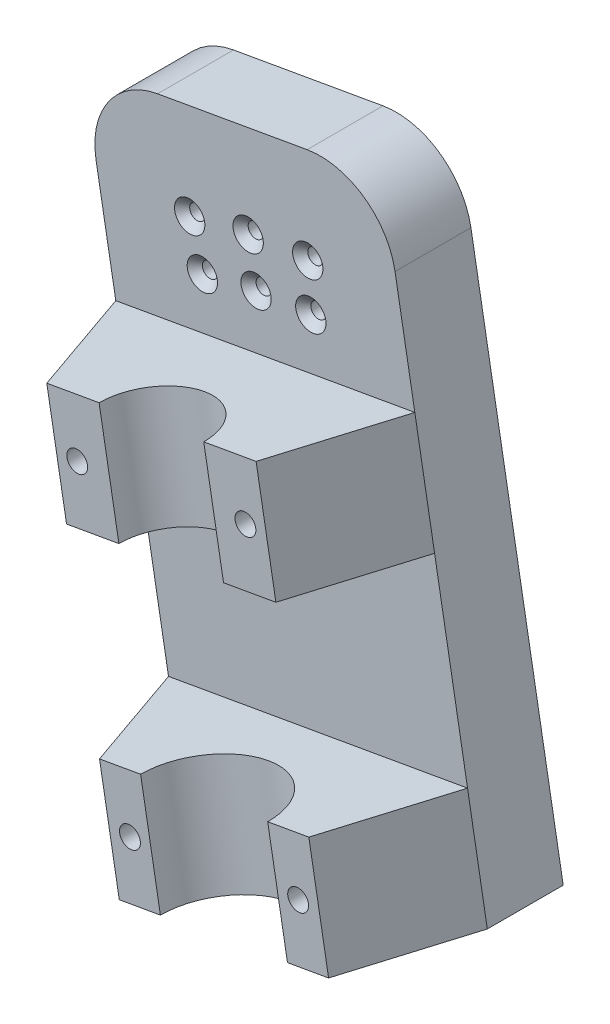
SolidWorks part; units mm, degrees
ref_plane "Front Plane" through (0, 0, 0) normal (0, 0, 1) x (1, 0, 0)
ref_plane "Top Plane" through (0, 0, 0) normal (0, 1, 0) x (1, 0, 0)
ref_plane "Right Plane" through (0, 0, 0) normal (1, 0, 0) x (0, 0, -1)
sketch "Sketch1" plane through (0, 0, 0) normal (0, 0, 1) x (1, 0, 0)
  line L0 (0, 62) -> (0, 74) construction
  line L1 (-20.5532, 71.0884) -> (-5, 73.8309) construction
  line L2 (0, 68) -> (0, 74)
  line L4 (0, 62) -> (0, 75.8947)
  line L5 (0, 0) -> (0, 79.9318) construction
  line L6 (0, 0) -> (-27.3383, 75.1113) construction
  line L7 (-27.3383, 75.1113) -> (-21.2052, 58.2609)
  line L8 (-20.5532, 71.0884) -> (0, 0) construction
  line L9 (0, 0) -> (-5, 73.8309) construction
  line L10 (-12.85, 72.8758) -> (-12.7766, 72.4597) construction
  line L13 (-12.7766, 72.4597) -> (-5.1015, 28.9321) construction
  line L16 (-5.1015, 28.9321) -> (-15.4722, 87.7473) construction
  line L17 (-34.6299, 81.2205) -> (4.7624, 88.1664)
  line L18 (-34.6299, 81.2205) -> (-20.738, 2.4359)
  line L19 (4.7624, 88.1664) -> (18.6543, 9.3818)
  line L20 (-20.738, 2.4359) -> (18.6543, 9.3818)
  arc A0 (0, 68) -> (-23.2574, 63.8991) centre (0, 0) ccw
  arc A1 (0, 74) -> (-25.3095, 69.5373) centre (0, 0) ccw
  arc A2 (-4.1389, 79.8245) -> (-27.3383, 75.1113) centre (0, 0) ccw
  arc A3 (0, 62) -> (-21.2052, 58.2609) centre (0, 0) ccw
  arc A5 (0, 75.8947) -> (-4.1389, 79.8245) centre (-3.9352, 75.8947) ccw
  circle A6 centre (-20.5532, 71.0884) radius 1
  circle A7 centre (-5, 73.8309) radius 1
  circle A8 centre (-18.8867, 65.3245) radius 1
  circle A9 centre (-4.5946, 67.8446) radius 1
  circle A10 centre (-12.85, 72.8758) radius 1
  circle A11 centre (-11.8081, 66.9669) radius 1
  point P31 (-80, 0)
  dimension "D1" = 79.9318
  dimension "D2" = 62
  dimension "D3" = 68
  dimension "D4" = 74
  dimension "D5" = 20
  dimension "D6" = 40
  dimension "D7" = 2
  dimension "D8" = 2
  dimension "D10" = 5
  dimension "D11" = 2
  dimension "D12" = 2
  dimension "D13" = 80
  dimension "D16" = 2
  dimension "D17" = 2
  dimension "D15" = 12
  dimension "D9" = 5
  dimension "D14" = 20
extrude "Boss-Extrude7" add sketch "Sketch1" along normal blind 10 contours L18 L20 L19 L17
extrude "Cut-Extrude4" cut sketch "Sketch1<9>" along normal blind 19 contours A6 | A7 | A9 | A8 | A10 | A11
sketch "Sketch1<9>" plane through (0, 0, 0) normal (0, 0, 1) x (1, 0, 0) same geometry as "Sketch1"
sketch "Sketch6" plane through (0, 0, 10) normal (0, 0, 1) x (1, 0, 0)
  line L0 (-23.3428, 17.208) -> (16.0495, 24.1539)
  line L1 (-27.684, 41.8282) -> (11.7083, 48.7741)
  line L2 (-30.2887, 56.6003) -> (9.1036, 63.5462)
  line L4 (4.7624, 88.1664) -> (-34.6299, 81.2205)
  line L5 (-34.6299, 81.2205) -> (-20.738, 2.4359)
  line L6 (-20.738, 2.4359) -> (18.6543, 9.3818)
  line L7 (18.6543, 9.3818) -> (4.7624, 88.1664)
  line L8 (4.7624, 88.1664) -> (-34.6299, 81.2205)
  line L9 (-34.6299, 81.2205) -> (-20.738, 2.4359)
  line L10 (-20.738, 2.4359) -> (18.6543, 9.3818)
  line L11 (18.6543, 9.3818) -> (4.7624, 88.1664)
  line M13 (-34.6299, 81.2205) -> (-20.738, 2.4359)
  line M14 (-20.738, 2.4359) -> (18.6543, 9.3818)
  line M15 (18.6543, 9.3818) -> (4.7624, 88.1664)
  dimension "D2" = 15
  dimension "D3" = 15
  dimension "D4" = 25
  dimension "D1" = 0
chamfer "Chamfer1" distance 1 angle 45 6 edges at (-19.8867, 65.3245, 10) (-5.5946, 67.8446, 10) (-6, 73.8309, 10) (-21.5532, 71.0884, 10) (-12.8081, 66.9669, 10) (-13.85, 72.8758, 10)
extrude "Boss-Extrude8" add sketch "Sketch6" along normal blind 30 contours L2 L1 M13 M15 | L0 M13 M14 M15 region at (-2.3443, 13.2949, 10) region at (-9.2902, 52.6872, 10)
sketch "Sketch7" plane through (-10.5925, 60.0733, 0) normal (-0.1736, 0.9848, 0) x (0.9848, 0.1736, 0)
  line L0 (0, -10) -> (0, -40) construction
  line L1 (0, -25) -> (-20, -25) construction
  line L2 (-20, -25) -> (20, -25) construction
  line L3 (-14, -10) -> (-14, -40) construction
  line L4 (20, -10) -> (-20, -10)
  line L5 (-20, -10) -> (-20, -40)
  line L6 (-20, -40) -> (20, -40)
  line L7 (20, -40) -> (20, -10)
  line L8 (20, -10) -> (-20, -10)
  line L9 (-20, -10) -> (-20, -40)
  line L10 (-20, -40) -> (20, -40)
  line L11 (20, -40) -> (20, -10)
  line L12 (14, -10) -> (14, -40) construction
  line L13 (-20, -10) -> (-14, -25)
  line L14 (-14, -25) -> (-8, -40)
  line L15 (20, -10) -> (14, -25)
  line L16 (14, -25) -> (8, -40)
  line L17 (-14, -25) -> (-7, -25)
  line L18 (-7, -25) -> (14, -25)
  circle A0 centre (0, -25) radius 7
  line M6 (-20, -10) -> (-20, -40)
  line M7 (-20, -40) -> (20, -40)
  line M8 (20, -40) -> (20, -10)
  dimension "D2" = 14
  dimension "D3" = 6
  dimension "D4" = 6
  dimension "D1" = 0
sketch "Sketch8" plane through (-3.6466, 20.681, 0) normal (-0.1736, 0.9848, 0) x (0.9848, 0.1736, 0)
  line L0 (0, -10) -> (0, -40) construction
  line L1 (-20, -25) -> (20, -25) construction
  line L2 (-8.5, -25) -> (-20, -25)
  line L3 (8.5, -25) -> (20, -25)
  line L4 (20, -10) -> (-20, -10)
  line L5 (-20, -10) -> (-20, -40)
  line L6 (-20, -40) -> (20, -40)
  line L7 (20, -40) -> (20, -10)
  line L8 (20, -10) -> (-20, -10)
  line L9 (-20, -10) -> (-20, -40)
  line L10 (-20, -40) -> (20, -40)
  line L11 (20, -40) -> (20, -10)
  line L12 (-14, -10) -> (-14, -40)
  line L13 (14, -40) -> (14, -10)
  line L14 (-20, -10) -> (-14, -25)
  line L15 (14, -25) -> (20, -10)
  line L16 (-20, -10) -> (-14, -25) construction
  line L17 (-14, -25) -> (-8, -40) construction
  line L18 (-8, -40) -> (8, -40) construction
  line L19 (20, -10) -> (14, -25) construction
  line L20 (14, -25) -> (8, -40) construction
  circle A0 centre (0, -25) radius 8.5
  line M6 (-20, -10) -> (-20, -40)
  line M7 (-20, -40) -> (20, -40)
  line M8 (20, -40) -> (20, -10)
  dimension "D2" = 17
  dimension "D3" = 6
  dimension "D4" = 6
  dimension "D1" = 0
extrude "Cut-Extrude7" cut sketch "Sketch8" along normal blind 42 and the other way blind 39 contours L14 L2 M6 | L12 L2 M6 M7 | L13 L3 M7 M8 | L15 L3 M8 region at (-20.3883, 17.7289, 32.5) region at (-21.3732, 17.5553, 20) region at (14.0799, 23.8066, 20) region at (13.0951, 23.633, 32.5)
extrude "Cut-Extrude8" cut sketch "Sketch8<4>" against normal blind 24 contours A0 | A0 L2 L12 L10 L13 L3 region at (-3.6466, 20.681, 33.9413) region at (-3.6466, 20.681, 25)
sketch "Sketch8<4>" plane through (-3.6466, 20.681, 0) normal (-0.1736, 0.9848, 0) x (0.9848, 0.1736, 0) same geometry as "Sketch8"
extrude "Cut-Extrude9" cut sketch "Sketch7" against normal blind 24 contours L14 L13 M6 M7 | A0 L17 L14 L10 L16 L18 | L15 L16 M7 M8 | L18 A0 | L18 A0 region at (5.1644, 62.8516, 30) region at (-26.3495, 57.2949, 30) region at (-10.5925, 60.0733, 32.9885) region at (-10.5925, 60.0733, 27.9709) region at (-10.5925, 60.0733, 22.0291)
sketch "Sketch10" plane through (0, 0, 25) normal (0, 0, 1) x (1, 0, 0)
  line L0 (-16.1316, 10.8638) -> (11.4431, 15.726) construction
  line L1 (10.1407, 23.112) -> (12.7454, 8.3399) construction
  line L2 (-14.7257, 18.7274) -> (-12.121, 3.9553) construction
  line L3 (7.4325, 22.6345) -> (10.0372, 7.8624) construction
  line L4 (-9.4128, 4.4328) -> (-12.0175, 19.205)
  line L5 (-12.0175, 19.205) -> (-17.4339, 18.2499)
  line L6 (-17.4339, 18.2499) -> (-14.8292, 3.4778)
  line L7 (-14.8292, 3.4778) -> (-9.4128, 4.4328)
  line L8 (-9.4128, 4.4328) -> (-12.0175, 19.205)
  line L9 (-12.0175, 19.205) -> (-17.4339, 18.2499)
  line L10 (-17.4339, 18.2499) -> (-14.8292, 3.4778)
  line L11 (-14.8292, 3.4778) -> (-9.4128, 4.4328)
  line L14 (7.329, 7.3849) -> (12.7454, 8.3399)
  line L15 (12.7454, 8.3399) -> (10.1407, 23.112)
  line L16 (10.1407, 23.112) -> (4.7243, 22.157)
  line L17 (4.7243, 22.157) -> (7.329, 7.3849)
  line L18 (7.329, 7.3849) -> (12.7454, 8.3399)
  line L19 (12.7454, 8.3399) -> (10.1407, 23.112)
  line L20 (10.1407, 23.112) -> (4.7243, 22.157)
  line L21 (4.7243, 22.157) -> (7.329, 7.3849)
  line L36 (-1.0942, 46.5167) -> (5.7995, 47.7322) construction
  line L37 (5.7995, 47.7322) -> (3.1948, 62.5043) construction
  line L38 (3.1948, 62.5043) -> (-3.6989, 61.2888) construction
  line L46 (-3.6989, 61.2888) -> (-1.0942, 46.5167) construction
  line L48 (-21.7751, 42.8701) -> (-14.8815, 44.0856) construction
  line L49 (-14.8815, 44.0856) -> (-17.4862, 58.8577) construction
  line L50 (-17.4862, 58.8577) -> (-24.3798, 57.6422) construction
  line L51 (-24.3798, 57.6422) -> (-21.7751, 42.8701) construction
  line L52 (-1.0942, 46.5167) -> (5.7995, 47.7322)
  line L53 (5.7995, 47.7322) -> (3.1948, 62.5043)
  line L54 (3.1948, 62.5043) -> (-3.6989, 61.2888)
  line L55 (-3.6989, 61.2888) -> (-1.0942, 46.5167)
  line L56 (-21.7751, 42.8701) -> (-14.8815, 44.0856)
  line L57 (-14.8815, 44.0856) -> (-17.4862, 58.8577)
  line L58 (-17.4862, 58.8577) -> (-24.3798, 57.6422)
  line L59 (-24.3798, 57.6422) -> (-21.7751, 42.8701)
  line L60 (-17.4339, 18.2499) -> (-21.7751, 42.8701) construction
  line L61 (-23.0775, 50.2561) -> (4.4971, 55.1183) construction
  line L62 (-21.7751, 42.8701) -> (-16.3587, 43.8251)
  line L63 (0.8755, 46.864) -> (5.7995, 47.7322)
  line L64 (-16.3587, 43.8251) -> (-18.9634, 58.5973)
  line L65 (-18.9634, 58.5973) -> (-24.3798, 57.6422)
  line L66 (3.1948, 62.5043) -> (-1.7293, 61.6361)
  line L67 (-24.3798, 57.6422) -> (-21.7751, 42.8701)
  line L68 (-1.7293, 61.6361) -> (0.8755, 46.864)
  line L69 (5.7995, 47.7322) -> (3.1948, 62.5043)
  line L70 (-21.6716, 58.1197) -> (-19.0669, 43.3476) construction
  line L71 (0.4865, 62.0268) -> (3.0913, 47.2547) construction
  line L72 (-24.3798, 57.6422) -> (-23.0775, 50.2561) construction
  line L73 (-23.0775, 50.2561) -> (-23.7287, 53.9492) construction
  line L74 (-23.7287, 53.9492) -> (3.846, 58.8113) construction
  line L75 (-19.6045, 30.56) -> (10.1407, 35.8049) construction
  circle A12 centre (-13.4233, 11.3414) radius 1.375
  circle A13 centre (8.7348, 15.2484) radius 1.375
  circle A14 centre (-20.3693, 50.7337) radius 1.375
  circle A15 centre (1.7889, 54.6408) radius 1.375
  point P49 (-21.0204, 54.4267)
  dimension "D3" = 5.5
  dimension "D4" = 2.75
  dimension "D5" = 2.75
  dimension "D6" = 2.75
  dimension "D10" = 2.75
  dimension "D11" = 2.75
  dimension "D7" = 7.5
  dimension "D8" = 3.75
  dimension "D9" = 5.5
  dimension "D1" = 0
  dimension "D2" = 0
extrude "Cut-Extrude10" cut sketch "Sketch10" against normal blind 7 contours A14 | A15 | A13 | A12
fillet "Fillet1" radius 10 2 edges at (4.7624, 88.1664, 5) (-34.6299, 81.2205, 5)
